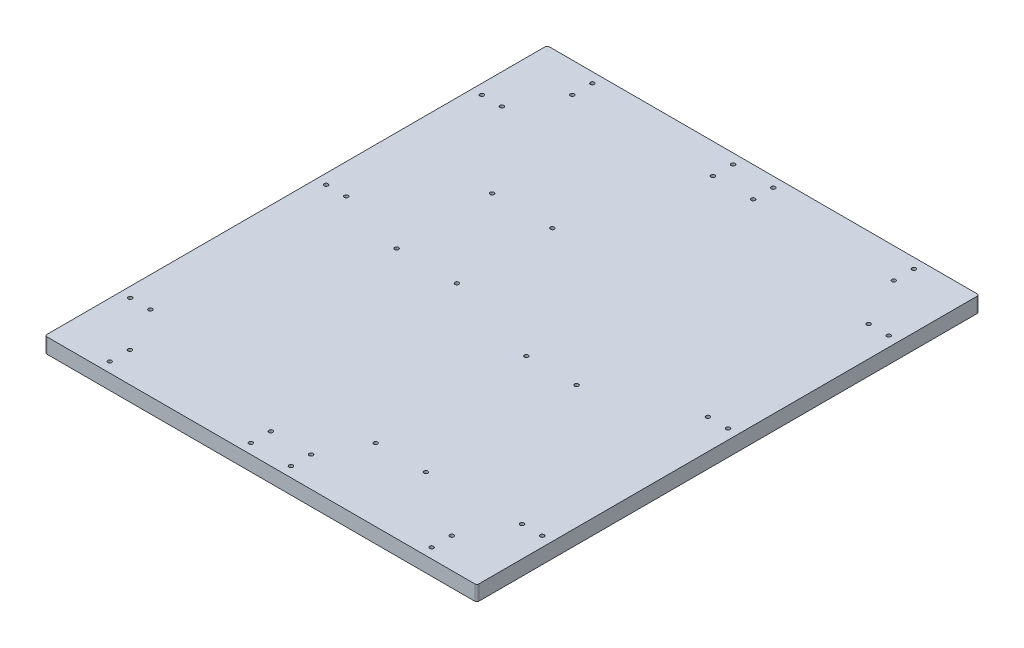
SolidWorks part; units mm, degrees
ref_plane "Front Plane" through (0, 0, 0) normal (0, 0, 1) x (1, 0, 0)
ref_plane "Top Plane" through (0, 0, 0) normal (0, 1, 0) x (1, 0, 0)
ref_plane "Right Plane" through (0, 0, 0) normal (1, 0, 0) x (0, 0, -1)
sketch "Sketch1" plane through (0, 0, 0) normal (0, 1, 0) x (1, 0, 0)
  line L1 (-215, -250) -> (215, -250)
  line L2 (-215, -250) -> (-215, 250)
  line L3 (-215, 250) -> (215, 250)
  line L4 (215, -250) -> (215, 250)
  line L5 (-215, -250) -> (215, 250) construction
  line L6 (-215, 250) -> (215, -250) construction
  point P0 (0, 0)
  dimension "D1" = 430
  dimension "D2" = 500
extrude "Boss-Extrude1" add sketch "Sketch1" along normal blind 15
sketch "Sketch6" plane through (0, 15, 0) normal (0, 1, 0) x (1, 0, 0)
  circle A0 centre (92.2927, -28) radius 1.95
  circle A1 centre (42.2927, -28) radius 1.95
  circle A2 centre (92.2927, -178) radius 1.95
  circle A3 centre (42.2927, -178) radius 1.95
  point P2 (31.6487, -154.3381)
  point P5 (44.9202, -170.4246)
  point P8 (49.2636, -175.4223)
  point P11 (42.4012, -178)
  point P12 (42.034, -177.7863)
  point P13 (42.6, -178)
  point P14 (91, -178)
  point P15 (69.7933, 46.3731)
  point P16 (69.7933, 46.3731)
  point P17 (41, -34.9407)
  point P18 (92.6, -28)
  point P19 (92.1182, -27.9089)
  point P20 (92.1201, -28)
  point P21 (41.9971, -28)
  point P22 (41.9971, -28)
  point P23 (91, -28)
  point P25 (0, 0)
  point P26 (91, -28)
  point P28 (91, -28)
  point P30 (92.1201, -178)
  point P31 (41.9971, -178)
  point P32 (42.2387, -178)
  point P33 (42.2927, -178)
  point P34 (0, 0)
  point P35 (42.2927, -28)
  point P36 (0, 0)
  point P37 (0, 0)
  point P38 (0, 0)
  point P39 (0, 0)
  point P40 (0, 0)
  dimension "D1" = 50
  dimension "D2" = 150
sketch "Sketch7" plane through (0, 15, 0) normal (0, 1, 0) x (1, 0, 0)
  circle A0 centre (-114.98, 95.1924) radius 1.95
  circle A1 centre (-54.98, 95.1924) radius 1.95
  circle A2 centre (-54.98, 0.1924) radius 1.95
  circle A3 centre (-114.98, 0.1924) radius 1.95
  point P2 (0, 0)
  point P5 (0, 0)
  point P8 (0, 0)
  point P11 (0, 0)
  dimension "D1" = 95
  dimension "D2" = 60
sketch "Sketch12" plane through (0, 0, 0) normal (0, -1, 0) x (-1, 0, 0)
  line L0 (215, -250) -> (-215, -250) construction
  line L1 (-215, 250) -> (215, 250) construction
  line L2 (215, 250) -> (215, -250) construction
  line L3 (-215, -250) -> (-215, 250) construction
  circle A0 centre (-185, -175) radius 1.95
  circle A1 centre (-205, 170) radius 1.95
  circle A3 centre (-185, 10) radius 1.95
  circle A4 centre (-205, 10) radius 1.95
  circle A5 centre (-205, -175) radius 1.95
  circle A6 centre (-185, 170) radius 1.95
  circle A7 centre (205, -175) radius 1.95
  circle A8 centre (205, 20) radius 1.95
  circle A9 centre (185, 175) radius 1.95
  circle A10 centre (205, 175) radius 1.95
  circle A11 centre (185, -175) radius 1.95
  circle A12 centre (185, 20) radius 1.95
  circle A13 centre (160.3499, -240) radius 1.95
  circle A14 centre (160.3499, -220) radius 1.95
  circle A15 centre (20, -240) radius 1.95
  circle A16 centre (20, -220) radius 1.95
  circle A17 centre (-20, -220) radius 1.95
  circle A19 centre (-20, -240) radius 1.95
  circle A20 centre (-160, -240) radius 1.95
  circle A21 centre (-160, -220) radius 1.95
  circle A22 centre (160, 220) radius 1.95
  circle A23 centre (160, 240) radius 1.95
  circle A24 centre (20, 220) radius 1.95
  circle A25 centre (20, 240) radius 1.95
  circle A26 centre (-20, 220) radius 1.95
  circle A27 centre (-20, 240) radius 1.95
  circle A28 centre (-160, 220) radius 1.95
  circle A29 centre (-160, 240) radius 1.95
  point P60 (0, 0)
  point P61 (0, 0)
  point P62 (0, 0)
  point P67 (187.633, 175.1082)
  point P68 (0, 0)
  point P69 (0, 0)
  point P70 (0, 0)
  point P71 (0, 0)
  point P72 (0, 0)
  point P73 (0, 0)
  dimension "D1" = 10
  dimension "D2" = 20
  dimension "D3" = 10
  dimension "D5" = 10
  dimension "D6" = 20
  dimension "D7" = 20
  dimension "D4" = 20
  dimension "D8" = 10
extrude "Cut-Extrude3" cut sketch "Sketch12" against normal blind 50.8
extrude "Cut-Extrude4" cut sketch "Sketch6" against normal blind 50.8
extrude "Cut-Extrude5" cut sketch "Sketch7" against normal blind 50.8
fillet "Fillet1" radius 2 4 edges at (215, 7.5, -250) (215, 7.5, 250) (-215, 7.5, 250) (-215, 7.5, -250)
